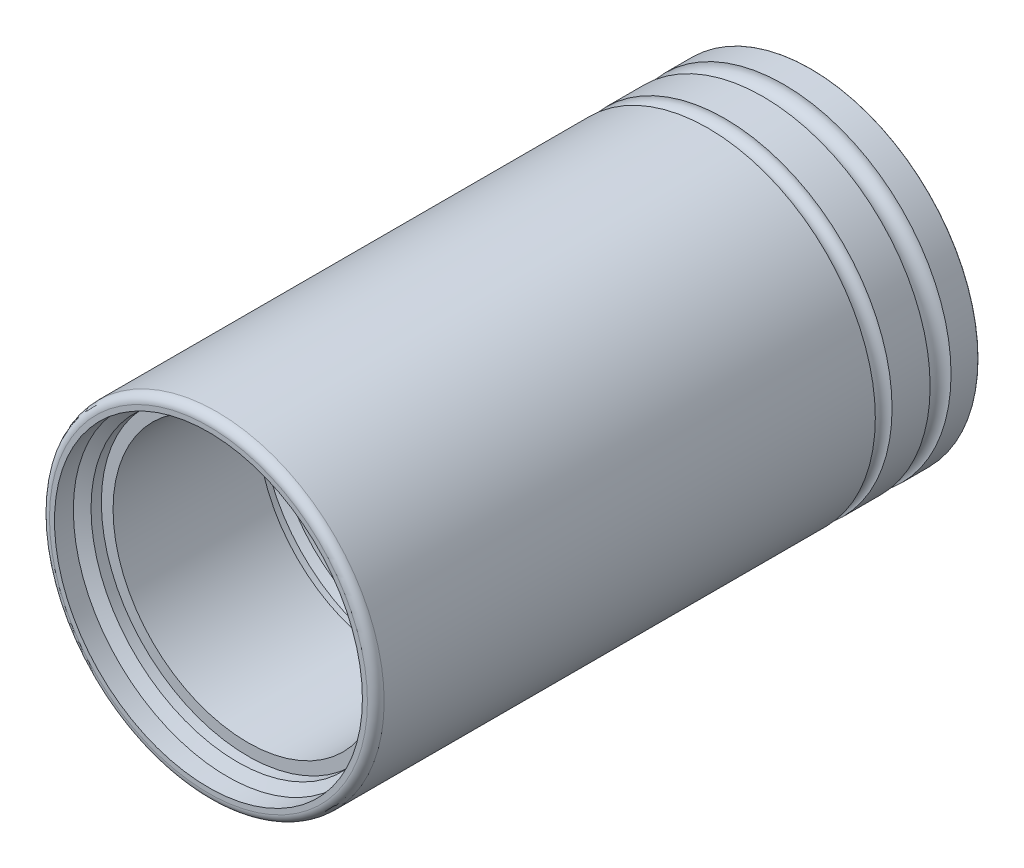
SolidWorks part; units mm, degrees
material "1.7319 (20MoCrS3)"
ref_plane "Спереди" through (0, 0, 0) normal (0, 0, 1) x (1, 0, 0)
ref_plane "Сверху" through (0, 0, 0) normal (0, 1, 0) x (1, 0, 0)
ref_plane "Справа" through (0, 0, 0) normal (1, 0, 0) x (0, 0, -1)
sketch "Эскиз1" plane through (0, 0, 0) normal (0, 0, 1) x (1, 0, 0)
  circle A0 centre (0, 0) radius 20
  dimension "D1" = 40
extrude "Бобышка-Вытянуть1" add sketch "Эскиз1" against normal blind 72
sketch "Эскиз4" plane through (0, 0, 0) normal (1, 0, 0) x (0, 0, -1)
  line L0 (0, 0) -> (0, 17.5)
  line L1 (0, 20) -> (0, -20) construction
  line L2 (0, 17.5) -> (4.7, 17.5)
  line L3 (4.7, 17.5) -> (4.7, 16.1)
  line L4 (4.7, 16.1) -> (22, 16.1)
  line L8 (22, 16.1) -> (22, 17.1)
  line L9 (22, 17.1) -> (23.4, 17.1)
  line L10 (23.4, 17.1) -> (23.9774, 16.1)
  line L14 (47, 6) -> (49, 6)
  line L15 (49, 6) -> (49, 9.5)
  line L16 (49, 9.5) -> (52.8, 9.5)
  line L20 (54, 9.5) -> (55.5, 9.5)
  line L21 (55.5, 9.5) -> (55.5, 10.75)
  line L22 (55.5, 10.75) -> (67, 10.75)
  line L23 (67, 10.75) -> (67, 12.4)
  line L24 (67, 12.4) -> (70, 12.4)
  line L25 (70, 12.4) -> (70, 10.75)
  line L26 (70, 10.75) -> (72, 10.75)
  line L27 (72, -20) -> (72, 20) construction
  line L28 (72, 10.75) -> (72, 0)
  line L29 (72, 0) -> (0, 0)
  line L32 (47, 16.1) -> (47, 6)
  line L33 (47, 16.1) -> (33.5, 16.1)
  line L35 (33.5, 16.1) -> (33.5, 18)
  line L36 (33.5, 18) -> (30.3, 18)
  line L37 (30.3, 16.1) -> (30.3, 18)
  line L38 (30.3, 16.1) -> (23.9774, 16.1)
  arc A0 (52.8, 9.5) -> (54, 9.5) centre (53.4, 9.5) cw
  dimension "D8" = 0.6
  dimension "D1" = 10.75
  dimension "D2" = 12.4
  dimension "D3" = 2
  dimension "D4" = 3
  dimension "D5" = 16.5
  dimension "D6" = 2.1
  dimension "D7" = 9.5
  dimension "D9" = 17.1
  dimension "D10" = 2
  dimension "D11" = 13.5
  dimension "D12" = 17.5
  dimension "D13" = 3.2
  dimension "D14" = 4.7
  dimension "D15" = 1.9
  dimension "D16" = 60
  dimension "D17" = 16.1
  dimension "D18" = 6
  dimension "D19" = 1.4
  dimension "D20" = 23
  dimension "D21" = 22
revolve "Вырез-Повернуть1" cut sketch "Эскиз4" angle 360 about L29
sketch "Эскиз5" plane through (0, 0, 0) normal (1, 0, 0) x (0, 0, -1)
  line L0 (3.466, 17.5) -> (1.734, 17.5)
  line L1 (1.734, 17.5) -> (2.6, 19)
  line L2 (2.6, 19) -> (3.466, 17.5)
  line L3 (4.7, 17.5) -> (4.7, -17.5) construction
  line L4 (4.7, 17.5) -> (4.7, -17.5) construction
  line L5 (0, 17.5) -> (0, -17.5) construction
  line L6 (0, 0) -> (8.2655, 0) construction
  line L7 (0, 20) -> (0, -20) construction
  line L8 (0, 20) -> (0, -20) construction
  point P3 (2.6, 17.5)
  dimension "D1" = 1
  dimension "D2" = 60
  dimension "D3" = 2.6
revolve "Вырез-Повернуть2" cut sketch "Эскиз5" angle 360 about L6
fillet "Скругление2" radius 1 1 edges at (20, 0, 0)
sketch "Эскиз6" plane through (0, 0, 0) normal (0, 0, 1) x (1, 0, 0)
  circle A2 centre (0, 0) radius 18.4
  dimension "D1" = 36.8
extrude "Вырез-Вытянуть1" cut sketch "Эскиз6" against normal blind 2.6
fillet "Скругление3" radius 0.05 3 edges at (-10.75, 0, -72) (20, 0, -72) (-6, 0, -49)
fillet "Скругление4" [suppressed] radius 0.1
fillet "Скругление5" [suppressed] radius 0.2
fillet "Скругление6" [suppressed] radius 0.4
fillet "Скругление7" [suppressed] radius 0.2
sketch "Эскиз7" plane through (0, 0, 0) normal (0, 1, 0) x (1, 0, 0)
  line L0 (19.95, 72) -> (-19.95, 72) construction
  line L1 (-15.75, 72) -> (-13.25, 72)
  line L2 (0, 88.9589) -> (0, 57.4428) construction
  arc A0 (-15.75, 72) -> (-13.25, 72) centre (-14.5, 72) cw
  dimension "D1" = 1.25
  dimension "D2" = 14.5
revolve "Повернуть1" add sketch "Эскиз7" angle 360 about L2
sketch "Эскиз8" plane through (0, 0, 0) normal (1, 0, 0) x (0, 0, -1)
  line L0 (1, -20) -> (1, 20) construction
  line L1 (1, -20) -> (1, 20) construction
  line L2 (67.5, 20) -> (40.6285, 20) construction
  line L7 (0, 0) -> (74.6339, 0) construction
  line L8 (72, -19.95) -> (72, 19.95) construction
  line L9 (72, -19.95) -> (72, 19.95) construction
  line L10 (71.95, 20) -> (1, 20) construction
  circle A0 centre (67.5, 20) radius 1.25
  circle A1 centre (60.7, 20) radius 1
  dimension "D1" = 2.5
  dimension "D3" = 2
  dimension "D4" = 6.8
  dimension "D2" = 4.5
  dimension "D5" = 20
revolve "Вырез-Повернуть3" cut sketch "Эскиз8" angle 360 about L7
fillet "Скругление10" [suppressed] radius 0.2
fillet "Скругление11" [suppressed] radius 0.2
